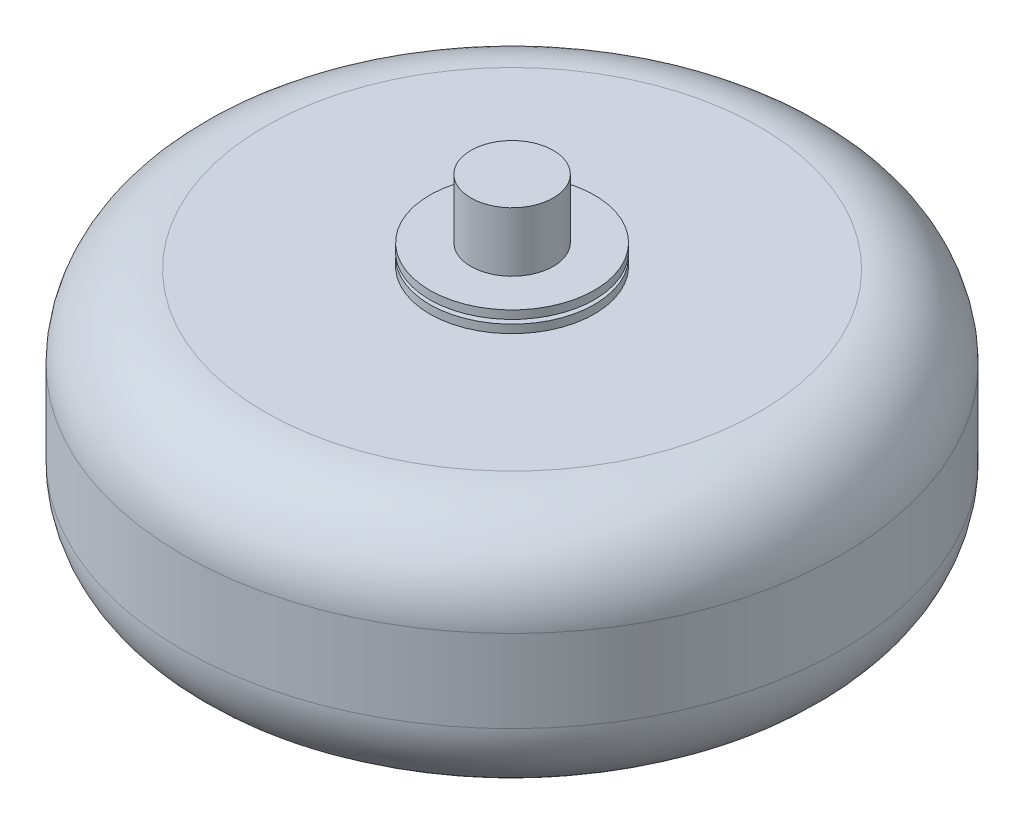
SolidWorks part; units mm, degrees
material "BUTYL"
ref_plane "Front Plane" through (0, 0, 0) normal (0, 0, 1) x (1, 0, 0)
ref_plane "Top Plane" through (0, 0, 0) normal (0, 1, 0) x (1, 0, 0)
ref_plane "Right Plane" through (0, 0, 0) normal (1, 0, 0) x (0, 0, -1)
sketch "Sketch1" plane through (0, 0, 0) normal (0, 1, 0) x (1, 0, 0)
  circle A0 centre (0, 0) radius 101.6
  dimension "D1" = 203.2
extrude "Boss-Extrude1" add sketch "Sketch1" along normal blind 38.1 and the other way blind 38.1 contours A0
sketch "Sketch2" plane through (0, -38.1, 0) normal (0, -1, 0) x (1, 0, 0)
  circle A0 centre (0, 0) radius 12.7
  dimension "D1" = 25.4
extrude "Cut-Extrude1" cut sketch "Sketch2" against normal blind 76.2
fillet "Fillet1" radius 25.4 2 edges at (0, 38.1, 101.6) (0, -38.1, 101.6)
ref_plane "Plane1" through (0, 0, 0) normal (0, 1, 0) x (1, 0, 0)
sketch "Sketch3" plane through (0, 0, 0) normal (0, 1, 0) x (1, 0, 0)
  circle A0 centre (0, 0) radius 12.7
  dimension "D1" = 25.4
extrude "Boss-Extrude2" add sketch "Sketch3" along normal blind 63.5 and the other way blind 63.5
ref_plane "Plane3" through (0, 42.672, 0) normal (0, 1, 0) x (1, 0, 0)
sketch "Sketch4" plane through (0, 42.672, 0) normal (0, 1, 0) x (1, 0, 0)
  circle A0 centre (0, 0) radius 25.4
  dimension "D1" = 50.8
extrude "Boss-Extrude3" add sketch "Sketch4" along normal blind 2.54 contours A0
ref_plane "Plane4" through (0, 41.402, 0) normal (0, 1, 0) x (1, 0, 0)
sketch "Sketch5" plane through (0, 41.402, 0) normal (0, 1, 0) x (1, 0, 0)
  circle A0 centre (0, 0) radius 25.4
  dimension "D1" = 50.8
extrude "Boss-Extrude4" add sketch "Sketch5" against normal blind 2.54
mirror "Mirror1" about plane through (0, 0, 0) normal (0, 1, 0) of "Boss-Extrude3", "Boss-Extrude4"
